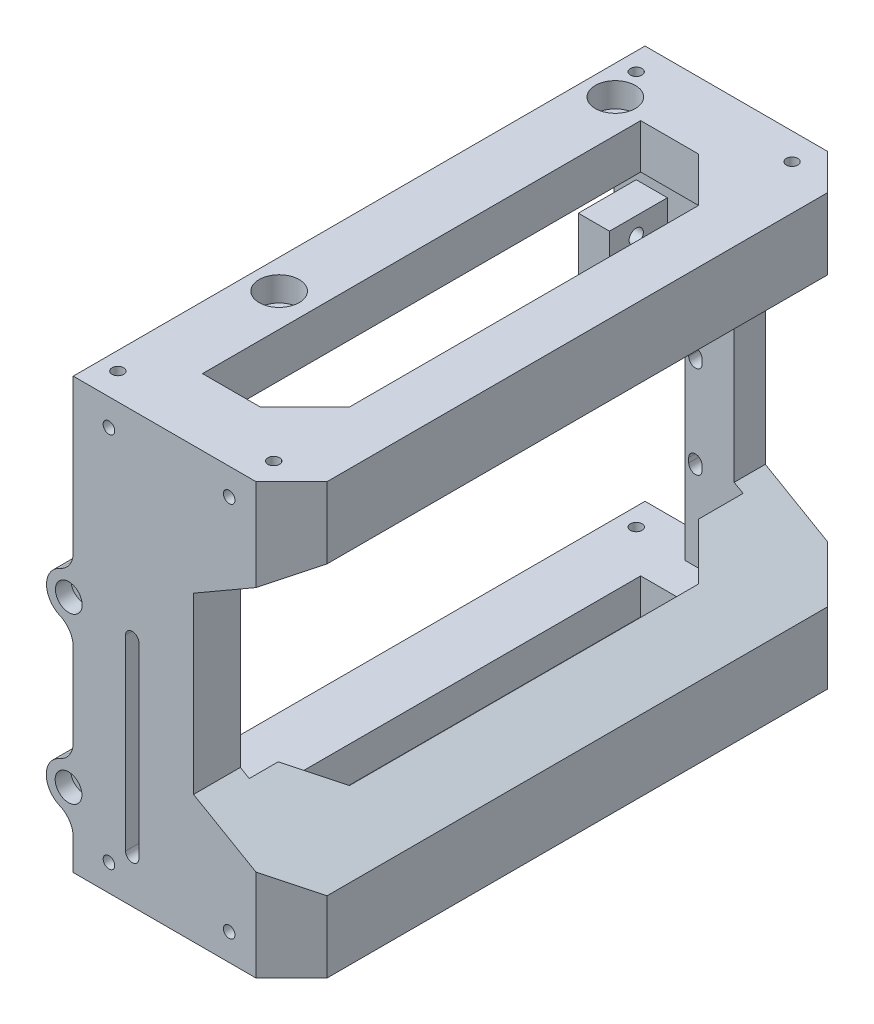
SolidWorks part; units mm, degrees
ref_plane "Front Plane" through (0, 0, 0) normal (0, 0, 1) x (1, 0, 0)
ref_plane "Top Plane" through (0, 0, 0) normal (0, 1, 0) x (1, 0, 0)
ref_plane "Right Plane" through (0, 0, 0) normal (1, 0, 0) x (0, 0, -1)
sketch "Sketch1" plane through (0, 0, 0) normal (0, 0, 1) x (1, 0, 0)
  line L0 (-612.6921, 563.5876) -> (-612.6921, 521.5876) construction
  line L1 (-615.6921, 521.5876) -> (-615.6921, 563.5876) construction
  line L2 (-612.6921, 563.5876) -> (-612.6921, 521.5876)
  line L3 (-615.6921, 521.5876) -> (-615.6921, 563.5876)
  line L4 (-600.414, 568.593) -> (-600.414, 523.593) construction
  line L5 (-631.4379, 608.0809) -> (-598.414, 608.0809)
  line L6 (-631.4379, 608.0809) -> (-631.4379, 511.53)
  line L7 (-631.4379, 511.53) -> (-598.414, 511.53)
  line L8 (-598.414, 608.0809) -> (-598.414, 511.53)
  line L9 (-610.478, 513.53) -> (-810.478, 513.53) construction
  line L11 (-615.8543, 598.0809) -> (-629.8543, 598.0809) construction
  arc A0 (-615.6921, 521.5876) -> (-612.6921, 521.5876) centre (-614.1921, 521.5876) ccw construction
  arc A1 (-612.6921, 563.5876) -> (-615.6921, 563.5876) centre (-614.1921, 563.5876) ccw construction
  arc A2 (-627.4205, 528.6438) -> (-629.5265, 526.5078) centre (-628.4914, 527.5934) ccw construction
  arc A3 (-629.5265, 526.5078) -> (-627.4205, 528.6438) centre (-628.4914, 527.5934) ccw construction
  arc A4 (-627.6878, 565.8925) -> (-629.1579, 563.2775) centre (-628.4379, 564.5934) ccw construction
  arc A5 (-629.1579, 563.2775) -> (-627.6878, 565.8925) centre (-628.4378, 564.5934) ccw construction
  arc A6 (-615.6921, 521.5876) -> (-612.6921, 521.5876) centre (-614.1921, 521.5876) ccw
  arc A7 (-612.6921, 563.5876) -> (-615.6921, 563.5876) centre (-614.1921, 563.5876) ccw
  arc A8 (-627.4205, 528.6438) -> (-629.5265, 526.5078) centre (-628.4914, 527.5934) ccw
  arc A9 (-629.5265, 526.5078) -> (-627.4205, 528.6438) centre (-628.4914, 527.5934) ccw
  arc A10 (-627.6878, 565.8925) -> (-629.1579, 563.2775) centre (-628.4379, 564.5934) ccw
  arc A11 (-629.1579, 563.2775) -> (-627.6878, 565.8925) centre (-628.4378, 564.5934) ccw
  dimension "D1" = 2
  dimension "D2" = 3
  dimension "D3" = 2
  dimension "D4" = 10
extrude "Boss-Extrude1" add sketch "Sketch1" along normal blind 10.5
sketch "Sketch2" plane through (-598.414, 0, 0) normal (1, 0, 0) x (0, 0, -1)
  line L0 (-10.5, 511.53) -> (0, 511.53) construction
  line L1 (-10.5, 608.0809) -> (117.9147, 608.0809)
  line L2 (-10.5, 608.0809) -> (-10.5, 511.53)
  line L3 (-10.5, 511.53) -> (117.9147, 511.53)
  line L4 (117.9147, 608.0809) -> (117.9147, 511.53)
  line L5 (-10.5, 511.53) -> (-10.5, 608.0809) construction
  dimension "D1" = 3
extrude "Boss-Extrude2" add sketch "Sketch2" along normal blind 10
sketch "Sketch3" plane through (0, 608.0809, 0) normal (0, 1, 0) x (1, 0, 0)
  line L0 (-598.414, 0) -> (-631.4379, 0) construction
  line L1 (-598.414, 117.9147) -> (-627.4379, 117.9147)
  line L2 (-598.414, 117.9147) -> (-598.414, 0)
  line L3 (-598.414, 0) -> (-627.4379, 0)
  line L4 (-627.4379, 117.9147) -> (-627.4379, 0)
  line L6 (-631.4379, -10.5) -> (-631.4379, 0) construction
  spline S0 degree 3 poles (-620.8554, 107.6647) (-626.8554, 107.6646) (-626.8553, 101.6646) (-620.8553, 101.6647) (-614.8553, 101.6648) (-614.8554, 107.6648) (-620.8554, 107.6647) (-626.8554, 107.6646) (-626.8553, 101.6646) knots -0.5 0 0 0 0.5 0.5 0.5 1 1 1 1.5 1.5 1.5 weights 1 0.333333 0.333333 1 0.333333 0.333333 1 0.333333 0.333333 only from (-620.8554, 107.6647) to (-620.8554, 107.6647) construction
  spline S1 degree 3 poles (-620.8544, 32.1647) (-626.8544, 32.1646) (-626.8543, 26.1646) (-620.8543, 26.1647) (-614.8543, 26.1648) (-614.8544, 32.1648) (-620.8544, 32.1647) (-626.8544, 32.1646) (-626.8543, 26.1646) knots -0.5 0 0 0 0.5 0.5 0.5 1 1 1 1.5 1.5 1.5 weights 1 0.333333 0.333333 1 0.333333 0.333333 1 0.333333 0.333333 only from (-620.8544, 32.1647) to (-620.8544, 32.1647) construction
  spline S2 degree 3 poles (-620.8554, 107.6647) (-626.8554, 107.6646) (-626.8553, 101.6646) (-620.8553, 101.6647) (-614.8553, 101.6648) (-614.8554, 107.6648) (-620.8554, 107.6647) (-626.8554, 107.6646) (-626.8553, 101.6646) knots -0.5 0 0 0 0.5 0.5 0.5 1 1 1 1.5 1.5 1.5 weights 1 0.333333 0.333333 1 0.333333 0.333333 1 0.333333 0.333333 only from (-620.8554, 107.6647) to (-620.8554, 107.6647)
  spline S3 degree 3 poles (-620.8544, 32.1647) (-626.8544, 32.1646) (-626.8543, 26.1646) (-620.8543, 26.1647) (-614.8543, 26.1648) (-614.8544, 32.1648) (-620.8544, 32.1647) (-626.8544, 32.1646) (-626.8543, 26.1646) knots -0.5 0 0 0 0.5 0.5 0.5 1 1 1 1.5 1.5 1.5 weights 1 0.333333 0.333333 1 0.333333 0.333333 1 0.333333 0.333333 only from (-620.8544, 32.1647) to (-620.8544, 32.1647)
  dimension "D1" = 4
extrude "Boss-Extrude3" add sketch "Sketch3" against normal blind 10
sketch "Sketch4" plane through (0, 511.53, 0) normal (0, -1, 0) x (1, 0, 0)
  line L0 (-598.414, -117.9147) -> (-627.4379, -117.9147) construction
  line L1 (-614.414, -117.9147) -> (-598.414, -117.9147)
  line L2 (-614.414, -117.9147) -> (-614.414, -110.9147)
  line L3 (-614.414, -110.9147) -> (-598.414, -110.9147)
  line L4 (-598.414, -117.9147) -> (-598.414, -110.9147)
  line L5 (-598.414, 0) -> (-598.414, -117.9147) construction
  dimension "D1" = 16
  dimension "D2" = 7
extrude "Boss-Extrude4" add sketch "Sketch4" against normal up to vertex (86.5508 mm away) up to point (-598.414, 598.0809, -117.9147)
sketch "Sketch5" plane through (0, 0, -117.9147) normal (0, 0, -1) x (-1, 0, 0)
  line L0 (610.6243, 538.9052) -> (610.6243, 539.9052) construction
  line L1 (607.6243, 539.9052) -> (607.6243, 538.9052) construction
  line L2 (610.6243, 559.61) -> (610.6243, 560.61) construction
  line L3 (607.6243, 560.61) -> (607.6243, 559.61) construction
  line L4 (610.6243, 538.9052) -> (610.6243, 539.9052)
  line L5 (607.6243, 539.9052) -> (607.6243, 538.9052)
  line L6 (610.6243, 559.61) -> (610.6243, 560.61)
  line L7 (607.6243, 560.61) -> (607.6243, 559.61)
  arc A0 (607.6243, 538.9052) -> (610.6243, 538.9052) centre (609.1243, 538.9052) ccw construction
  arc A1 (610.6243, 539.9052) -> (607.6243, 539.9052) centre (609.1243, 539.9052) ccw construction
  arc A2 (607.6243, 559.61) -> (610.6243, 559.61) centre (609.1243, 559.61) ccw construction
  arc A3 (610.6243, 560.61) -> (607.6243, 560.61) centre (609.1243, 560.61) ccw construction
  arc A4 (607.6243, 538.9052) -> (610.6243, 538.9052) centre (609.1243, 538.9052) ccw
  arc A5 (610.6243, 539.9052) -> (607.6243, 539.9052) centre (609.1243, 539.9052) ccw
  arc A6 (607.6243, 559.61) -> (610.6243, 559.61) centre (609.1243, 559.61) ccw
  arc A7 (610.6243, 560.61) -> (607.6243, 560.61) centre (609.1243, 560.61) ccw
extrude "Cut-Extrude1" cut sketch "Sketch5" against normal blind 10
sketch "Sketch6" plane through (0, 0, -117.9147) normal (0, 0, -1) x (-1, 0, 0)
  line L0 (588.414, 511.53) -> (588.414, 608.0809) construction
  line L1 (631.4379, 511.53) -> (588.414, 511.53)
  line L2 (631.4379, 511.53) -> (631.4379, 519.53)
  line L3 (631.4379, 519.53) -> (588.414, 519.53)
  line L4 (588.414, 511.53) -> (588.414, 519.53)
  dimension "D1" = 8
extrude "Boss-Extrude5" add sketch "Sketch6" against normal blind 115
sketch "Sketch7" plane through (-588.414, 0, 0) normal (1, 0, 0) x (0, 0, -1)
  line L0 (110.9147, 519.53) -> (117.9147, 519.53) construction
  line L1 (4.9147, 563.53) -> (110.9147, 563.53)
  line L2 (4.9147, 563.53) -> (4.9147, 519.53)
  line L3 (4.9147, 519.53) -> (110.9147, 519.53)
  line L4 (110.9147, 563.53) -> (110.9147, 519.53)
  line L5 (110.9147, 598.0809) -> (110.9147, 519.53) construction
  dimension "D1" = 106
  dimension "D2" = 44
extrude "Cut-Extrude2" cut sketch "Sketch7" against normal blind 115
sketch "Sketch8" plane through (0, 0, -117.9147) normal (0, 0, -1) x (-1, 0, 0)
  line L0 (588.414, 511.53) -> (631.4379, 511.53) construction
  line L1 (588.414, 608.0809) -> (578.414, 608.0809)
  line L2 (588.414, 608.0809) -> (588.414, 511.53)
  line L3 (588.414, 511.53) -> (578.414, 511.53)
  line L4 (578.414, 608.0809) -> (578.414, 511.53)
  dimension "D1" = 10
extrude "Boss-Extrude6" add sketch "Sketch8" against normal up to vertex (128.4147 mm away) up to point (-588.414, 608.0809, 10.5)
sketch "Sketch9" plane through (0, 0, -117.9147) normal (0, 0, -1) x (-1, 0, 0)
  line L0 (578.414, 592.0809) -> (578.414, 527.53)
  line L1 (578.414, 608.0809) -> (578.414, 511.53) construction
  line L2 (578.414, 527.53) -> (600.414, 540.2317)
  line L3 (600.414, 540.2317) -> (600.414, 579.3792)
  line L4 (600.414, 579.3792) -> (578.414, 592.0809)
  line L5 (578.414, 592.0809) -> (578.414, 527.53)
  line L6 (578.414, 608.0809) -> (627.4379, 608.0809) construction
  line L7 (578.414, 511.53) -> (631.4379, 511.53) construction
  line M14 (578.414, 608.0809) -> (578.414, 511.53)
  dimension "D1" = 16
  dimension "D2" = 16
  dimension "D3" = 60
  dimension "D4" = 22
extrude "Cut-Extrude3" cut sketch "Sketch9" against normal blind 210 contours L3 L4 L2 M14 region at (-588.5158, 559.8055, -117.9147)
chamfer "Chamfer1" distance 8 angle 45 4 edges at (-578.414, 600.0809, -117.9147) (-578.414, 519.53, -117.9147) (-578.414, 600.0809, 10.5) (-578.414, 519.53, 10.5)
sketch "Sketch10" plane through (0, 608.0809, 0) normal (0, 1, 0) x (1, 0, 0)
  line L0 (-586.414, 117.9147) -> (-627.4379, 117.9147) construction
  line L1 (-613.414, 102.9147) -> (-600.414, 102.9147)
  line L2 (-613.414, 102.9147) -> (-613.414, 4.5)
  line L3 (-613.414, 4.5) -> (-600.414, 4.5)
  line L4 (-590.414, 92.9147) -> (-590.414, 14.5)
  line L5 (-586.414, -10.5) -> (-631.4379, -10.5) construction
  line L6 (-578.414, -2.5) -> (-578.414, 109.9147) construction
  line L7 (-600.414, 102.9147) -> (-590.414, 92.9147)
  line L8 (-600.414, 4.5) -> (-590.414, 14.5)
  point P1 (-590.414, 4.5)
  point P3 (-590.414, 102.9147)
  dimension "D1" = 15
  dimension "D2" = 15
  dimension "D3" = 12
  dimension "D4" = 23
extrude "Cut-Extrude4" cut sketch "Sketch10" against normal blind 210
sketch "Sketch11" plane through (-627.4379, 0, 0) normal (-1, 0, 0) x (0, 0, 1)
  line L1 (-128.8978, 612.3644) -> (20.2748, 612.3644)
  line L2 (-128.8978, 612.3644) -> (-128.8978, 509.0124)
  line L3 (-128.8978, 509.0124) -> (20.2748, 509.0124)
  line L4 (20.2748, 612.3644) -> (20.2748, 509.0124)
extrude "Cut-Extrude5" cut sketch "Sketch11" along normal blind 16
sketch "Sketch12" plane through (0, 0, 10.5) normal (0, 0, 1) x (1, 0, 0)
  arc A0 (-627.4379, 526.5257) -> (-627.4205, 528.6438) centre (-628.4914, 527.5934) ccw construction
  arc A1 (-627.4379, 563.4754) -> (-627.4379, 565.7115) centre (-628.4378, 564.5934) ccw construction
  circle A2 centre (-628.4914, 527.5934) radius 1.5
  circle A3 centre (-628.4378, 564.5934) radius 1.5
  circle A4 centre (-628.4378, 564.5934) radius 5
  circle A5 centre (-628.4914, 527.5934) radius 5
  dimension "D1" = 10
extrude "Boss-Extrude7" add sketch "Sketch12" against normal up to vertex (10.5 mm away) up to point (-627.4379, 563.4754, 0)
fillet "Fillet1" radius 5 4 edges at (-627.4379, 522.7057, 5.25) (-627.4379, 532.4812, 5.25) (-627.4379, 569.4924, 5.25) (-627.4379, 559.6944, 5.25)
sketch "Sketch13" plane through (0, 519.53, 0) normal (0, 1, 0) x (1, 0, 0)
  line L0 (-598.414, 4.9147) -> (-598.414, 6.5)
  line L1 (-600.414, 4.5) -> (-590.414, 14.5) construction
  line L2 (-590.414, 92.9147) -> (-600.414, 102.9147) construction
  line L3 (-590.414, 14.5) -> (-590.414, 92.9147) construction
  line L4 (-590.414, 92.9147) -> (-598.414, 100.9147)
  line L5 (-590.414, 14.5) -> (-590.414, 92.9147)
  line L6 (-598.414, 6.5) -> (-590.414, 14.5)
  line L8 (-614.414, 117.9147) -> (-627.4379, 117.9147)
  line L9 (-627.4379, 117.9147) -> (-627.4379, 2.9147)
  line L10 (-627.4379, 2.9147) -> (-598.414, 2.9147)
  line L11 (-598.414, 2.9147) -> (-598.414, 4.9147)
  line L12 (-598.414, 4.9147) -> (-588.414, 4.9147)
  line L13 (-588.414, 4.9147) -> (-588.414, 110.9147)
  line L14 (-588.414, 110.9147) -> (-614.414, 110.9147)
  line L15 (-614.414, 110.9147) -> (-614.414, 117.9147)
  line L20 (-598.414, 4.9147) -> (-588.414, 4.9147)
  line L21 (-588.414, 4.9147) -> (-588.414, 110.9147)
  line L22 (-588.414, 110.9147) -> (-598.414, 110.9147)
  line L24 (-598.414, 100.9147) -> (-598.414, 110.9147)
  dimension "D1" = 0
extrude "Boss-Extrude8" add sketch "Sketch13" along normal up to surface (14.9282 mm away) up to face at (-592.0807, 535.4205, -46.1586)
sketch "Sketch14" plane through (0, 0, -117.9147) normal (0, 0, -1) x (-1, 0, 0)
  line L0 (609.1243, 560.61) -> (609.1243, 559.61) construction
  line L1 (614.9243, 560.61) -> (614.9243, 559.61)
  line L2 (603.3243, 560.61) -> (603.3243, 559.61)
  line L3 (609.1243, 539.9052) -> (609.1243, 538.9052) construction
  line L4 (614.9243, 539.9052) -> (614.9243, 538.9052)
  line L5 (603.3243, 539.9052) -> (603.3243, 538.9052)
  arc A0 (614.9243, 560.61) -> (603.3243, 560.61) centre (609.1243, 560.61) ccw
  arc A1 (603.3243, 559.61) -> (614.9243, 559.61) centre (609.1243, 559.61) ccw
  arc A2 (614.9243, 539.9052) -> (603.3243, 539.9052) centre (609.1243, 539.9052) ccw
  arc A3 (603.3243, 538.9052) -> (614.9243, 538.9052) centre (609.1243, 538.9052) ccw
  point P4 (609.1243, 560.11)
  point P9 (609.1243, 539.4052)
  dimension "D1" = 5.8
extrude "Cut-Extrude6" cut sketch "Sketch14" against normal blind 3.5
sketch "Sketch15" plane through (0, 608.0809, 0) normal (0, 1, 0) x (1, 0, 0)
  circle A0 centre (-620.8544, 29.1647) radius 4.5
  circle A1 centre (-620.8553, 104.6647) radius 4.5
  dimension "D1" = 9
extrude "Cut-Extrude7" cut sketch "Sketch15" against normal blind 5.5
sketch "Sketch16" plane through (0, 602.5809, 0) normal (0, 1, 0) x (1, 0, 0)
  circle A0 centre (-620.8553, 104.6647) radius 3
  circle A1 centre (-620.8553, 104.6647) radius 2.65
  circle A2 centre (-620.8544, 29.1647) radius 3
  circle A3 centre (-620.8544, 29.1647) radius 2.65
  dimension "D1" = 5.3
extrude "Boss-Extrude9" add sketch "Sketch16" against normal up to vertex (4.5 mm away) up to point (-627.4379, 598.0809, -117.9147)
sketch "Sketch17" plane through (0, 0, 10.5) normal (0, 0, 1) x (1, 0, 0)
  circle A0 centre (-628.4378, 564.5934) radius 3
  circle A1 centre (-628.4914, 527.5934) radius 3
  dimension "D1" = 6
extrude "Cut-Extrude8" cut sketch "Sketch17" against normal blind 3.5
sketch "Sketch18" plane through (0, 0, -117.9147) normal (0, 0, -1) x (-1, 0, 0)
  line L0 (614.414, 598.0809) -> (614.414, 562.989) construction
  line L1 (627.4379, 598.0809) -> (614.414, 598.0809)
  line L2 (627.4379, 598.0809) -> (627.4379, 563.0809)
  line L3 (627.4379, 563.0809) -> (614.414, 563.0809)
  line L4 (614.414, 598.0809) -> (614.414, 563.0809)
  dimension "D1" = 35
extrude "Boss-Extrude10" add sketch "Sketch18" against normal up to vertex (7 mm away) up to point (-614.414, 598.0809, -110.9147)
sketch "Sketch19" plane through (0, 598.0809, 0) normal (0, -1, 0) x (1, 0, 0)
  line L1 (-627.4379, -110.9147) -> (-615.4379, -110.9147)
  line L2 (-627.4379, -110.9147) -> (-627.4379, -112.9147)
  line L3 (-627.4379, -112.9147) -> (-615.4379, -112.9147)
  line L4 (-615.4379, -110.9147) -> (-615.4379, -112.9147)
  dimension "D1" = 12
  dimension "D2" = 2
extrude "Cut-Extrude9" cut sketch "Sketch19" along normal blind 3
ref_plane "Plane1" through (-615.414, 0, 0) normal (1, 0, 0) x (0, 0, -1)
sketch "Sketch20" plane through (-615.414, 0, 0) normal (1, 0, 0) x (0, 0, -1)
  line L0 (110.9147, 579.3792) -> (110.9147, 540.2317) construction
  line L1 (110.9147, 563.0809) -> (97.9147, 563.0809)
  line L2 (110.9147, 563.0809) -> (110.9147, 588.0809)
  line L3 (110.9147, 588.0809) -> (97.9147, 588.0809)
  line L4 (97.9147, 563.0809) -> (97.9147, 588.0809)
  line L6 (3, 563.0809) -> (13, 563.0809)
  line L7 (0, 581.0809) -> (0, 598.0809)
  line L8 (0, 598.0809) -> (13, 598.0809)
  line L9 (13, 563.0809) -> (13, 598.0809)
  line L13 (0, 581.0809) -> (3, 581.0809)
  line L14 (3, 563.0809) -> (3, 581.0809)
  dimension "D1" = 25
  dimension "D2" = 3
  dimension "D3" = 18
  dimension "D4" = 13
  dimension "D5" = 10
extrude "Boss-Extrude11" add sketch "Sketch20" against normal blind 7
sketch "Sketch22" plane through (-615.414, 0, 0) normal (1, 0, 0) x (0, 0, -1)
  line L0 (0, 598.0809) -> (0, 581.0809) construction
  line L1 (7, 568.0809) -> (103.9147, 568.0809) construction
  line L2 (7, 568.0809) -> (7, 584.0809) construction
  line L3 (7, 584.0809) -> (103.9147, 584.0809) construction
  line L4 (103.9147, 568.0809) -> (103.9147, 584.0809) construction
  line L5 (110.9147, 563.0809) -> (110.9147, 588.0809) construction
  line L6 (3, 563.0809) -> (13, 563.0809) construction
  line L7 (110.9147, 588.0809) -> (97.9147, 588.0809) construction
  circle A0 centre (7, 584.0809) radius 1.6
  circle A1 centre (7, 568.0809) radius 1.6
  circle A2 centre (103.9147, 584.0809) radius 1.6
  circle A3 centre (103.9147, 568.0809) radius 1.6
  dimension "D1" = 3.2
  dimension "D5" = 4
  dimension "D2" = 7
  dimension "D3" = 7
  dimension "D4" = 5
extrude "Cut-Extrude10" cut sketch "Sketch22" against normal blind 10
sketch "Sketch23" plane through (-622.414, 0, 0) normal (-1, 0, 0) x (0, 0, 1)
  line L1 (-4.1, 569.7552) -> (-7, 571.4295)
  line L2 (-7, 571.4295) -> (-9.9, 569.7552)
  line L3 (-9.9, 569.7552) -> (-9.9, 566.4066)
  line L4 (-9.9, 566.4066) -> (-7, 564.7322)
  line L5 (-7, 564.7322) -> (-4.1, 566.4066)
  line L6 (-4.1, 566.4066) -> (-4.1, 569.7552)
  line L7 (-4.1, 585.7552) -> (-7, 587.4295)
  line L8 (-7, 587.4295) -> (-9.9, 585.7552)
  line L9 (-9.9, 585.7552) -> (-9.9, 582.4066)
  line L10 (-9.9, 582.4066) -> (-7, 580.7322)
  line L11 (-7, 580.7322) -> (-4.1, 582.4066)
  line L12 (-4.1, 582.4066) -> (-4.1, 585.7552)
  line L13 (-103.9147, 571.4295) -> (-106.8147, 569.7552)
  line L14 (-106.8147, 569.7552) -> (-106.8147, 566.4066)
  line L15 (-106.8147, 566.4066) -> (-103.9147, 564.7322)
  line L16 (-103.9147, 564.7322) -> (-101.0147, 566.4066)
  line L17 (-101.0147, 566.4066) -> (-101.0147, 569.7552)
  line L18 (-101.0147, 569.7552) -> (-103.9147, 571.4295)
  line L19 (-106.8147, 585.7552) -> (-106.8147, 582.4066)
  line L20 (-106.8147, 582.4066) -> (-103.9147, 580.7322)
  line L21 (-103.9147, 580.7322) -> (-101.0147, 582.4066)
  line L22 (-101.0147, 582.4066) -> (-101.0147, 585.7552)
  line L23 (-101.0147, 585.7552) -> (-103.9147, 587.4295)
  line L24 (-103.9147, 587.4295) -> (-106.8147, 585.7552)
  circle A0 centre (-7, 568.0809) radius 2.9 construction
  circle A1 centre (-7, 584.0809) radius 2.9 construction
  circle A2 centre (-103.9147, 568.0809) radius 2.9 construction
  circle A3 centre (-103.9147, 584.0809) radius 2.9 construction
  dimension "D1" = 5.8
extrude "Cut-Extrude11" cut sketch "Sketch23" against normal blind 3.5
sketch "Sketch26" plane through (0, 511.53, 0) normal (0, -1, 0) x (1, 0, 0)
  circle A0 centre (-623.414, 4.5) radius 1.3
  circle A1 centre (-588.414, 4.5) radius 1.3
  circle A2 centre (-623.414, -111.9147) radius 1.3
  circle A3 centre (-588.414, -111.9147) radius 1.3
  dimension "D1" = 2.6
extrude "Cut-Extrude13" cut sketch "Sketch26" against normal blind 12
sketch "Sketch27" plane through (0, 0, 10.5) normal (0, 0, 1) x (1, 0, 0)
  circle A0 centre (-619.414, 602.0809) radius 1.3
  circle A1 centre (-592.414, 602.0809) radius 1.3
  circle A2 centre (-619.414, 517.53) radius 1.3
  circle A3 centre (-592.414, 517.53) radius 1.3
  dimension "D1" = 2.6
extrude "Cut-Extrude14" cut sketch "Sketch27" against normal blind 12
sketch "Sketch28" plane through (0, 608.0809, 0) normal (0, 1, 0) x (1, 0, 0)
  circle A0 centre (-623.414, 111.9147) radius 1.3
  circle A1 centre (-588.414, 111.9147) radius 1.3
  circle A2 centre (-623.414, -4.5) radius 1.3
  circle A3 centre (-588.414, -4.5) radius 1.3
  point P12 (0, 0)
  point P13 (0, 0)
  point P14 (0, 0)
  point P15 (0, 0)
  point P16 (0, 0)
  dimension "D1" = 2.6
extrude "Cut-Extrude15" cut sketch "Sketch28" against normal blind 12
sketch "Sketch29" plane through (0, 0, -117.9147) normal (0, 0, -1) x (-1, 0, 0)
  circle A0 centre (592.414, 602.0809) radius 1.3
  circle A1 centre (619.414, 602.0809) radius 1.3
  circle A2 centre (592.414, 517.53) radius 1.3
  circle A3 centre (619.414, 517.53) radius 1.3
  dimension "D1" = 2.6
extrude "Cut-Extrude16" cut sketch "Sketch29" against normal blind 12
sketch "Sketch30" plane through (0, 598.0809, 0) normal (0, -1, 0) x (1, 0, 0)
  line L0 (-627.4379, -112.9147) -> (-627.4379, 0) construction
  line L1 (-625.8544, -29.1647) -> (-627.4379, -29.1647)
  line L2 (-620.8553, -34.1647) -> (-620.8553, -99.6647)
  line L3 (-625.8553, -104.6647) -> (-627.4379, -104.6647)
  line L4 (-627.4379, -29.1647) -> (-627.4379, -104.6647)
  arc A0 (-625.8544, -29.1647) -> (-620.8553, -34.1647) centre (-620.8544, -29.1647) ccw
  arc A1 (-620.8553, -99.6647) -> (-625.8553, -104.6647) centre (-620.8553, -104.6647) ccw
  circle A2 centre (-620.8553, -104.6647) radius 2.65 construction
  point P3 (-627.4379, -104.6647)
  point P11 (0, 0)
  point P12 (-620.8553, -104.6647)
  dimension "D1" = 10
extrude "Cut-Extrude17" cut sketch "Sketch30" against normal blind 5
chamfer "Chamfer2" distance 3 angle 45 1 edges at (-614.414, 541.3055, -110.9147)
